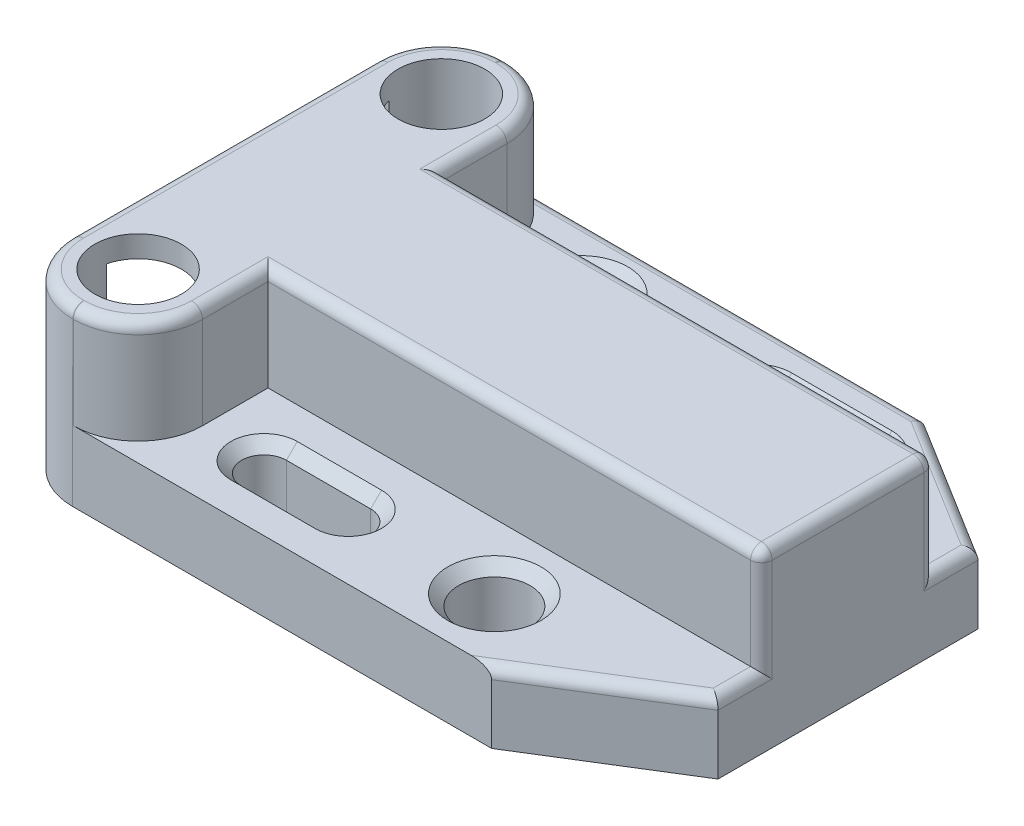
SolidWorks part; units mm, degrees
ref_plane "Front Plane" through (0, 0, 0) normal (0, 0, 1) x (1, 0, 0)
ref_plane "Top Plane" through (0, 0, 0) normal (0, 1, 0) x (1, 0, 0)
ref_plane "Right Plane" through (0, 0, 0) normal (1, 0, 0) x (0, 0, -1)
sketch "Sketch1" plane through (0, 0, 0) normal (0, 1, 0) x (1, 0, 0)
  line L0 (33.1051, 2.8562) -> (46.002, -5.1438)
  line L1 (-3.6889, 2.8562) -> (33.1051, 2.8562)
  line L2 (-11.5449, -3.9662) -> (-11.5449, -29.6573)
  line L3 (-5.3262, -37.1438) -> (33.1051, -37.1438)
  line L4 (33.1051, 2.8562) -> (33.1051, -37.1438)
  line L5 (46.002, -5.1438) -> (46.002, -29.1438)
  line L6 (46.002, -29.1438) -> (33.1051, -37.1438)
  line L10 (-3.6889, 2.8562) -> (-5.5949, 2.8562)
  line L11 (-11.5449, -3.9662) -> (-11.5449, -3.0938)
  line L13 (-11.5449, -29.6573) -> (-11.5449, -31.1938)
  line L14 (-5.5949, -37.1438) -> (-5.3262, -37.1438)
  arc A0 (-11.5449, -31.1938) -> (-5.5949, -37.1438) centre (-5.5949, -31.1938) ccw
  arc A1 (-5.5949, 2.8562) -> (-11.5449, -3.0938) centre (-5.5949, -3.0938) ccw
  point P14 (46.002, -17.1438)
  dimension "D4" = 5.95
  dimension "D1" = 57.5469
  dimension "D2" = 40
  dimension "D3" = 24
  dimension "D5" = 44.65
extrude "Boss-Extrude1" add sketch "Sketch1" along normal blind 6.5 contours L1 A1 L2 L3 L4 | L6 L5 L0 L4 region at (10.9602, 0, 17.1438) region at (39.0162, 0, 17.1438)
sketch "Sketch2" plane through (0, 6.5, 0) normal (0, 1, 0) x (1, 0, 0)
  line L0 (-5.5949, 2.8562) -> (33.1051, 2.8562) construction
  line L1 (46.002, -9.1438) -> (0.4551, -9.1438)
  line L2 (46.002, -9.1438) -> (46.002, -25.1438)
  line L3 (46.002, -25.1438) -> (0.4551, -25.1438)
  line L4 (0.4551, -9.1438) -> (0.4551, -25.1438)
  line L5 (-5.5949, 2.8562) -> (-5.4949, 2.8562)
  line L6 (-11.5449, -3.0938) -> (-11.5449, -31.1938)
  line L7 (-5.5949, -37.1438) -> (-5.4949, -37.1438)
  line L8 (0.4551, -3.0938) -> (0.4551, -31.1938)
  line L9 (-5.5949, -37.1438) -> (33.1051, -37.1438) construction
  line L10 (46.002, -5.1438) -> (46.002, -29.1438) construction
  line L11 (-11.5449, -3.0938) -> (-11.5449, -31.1938) construction
  circle A0 centre (-5.5449, -3.1438) radius 4
  circle A1 centre (-5.5449, -31.1438) radius 4
  arc A3 (-5.5199, -37.1438) -> (0.4551, -31.1938) centre (-5.4949, -31.1938) ccw
  arc A4 (-11.5449, -31.1938) -> (-5.5699, -37.1438) centre (-5.5949, -31.1938) ccw
  arc A5 (-5.4949, 2.8562) -> (0.4551, -3.0938) centre (-5.4949, -3.0938) cw
  arc A6 (-5.5949, 2.8562) -> (-11.5449, -3.0938) centre (-5.5949, -3.0938) ccw
  arc A7 (-5.5199, -37.1438) -> (-5.5699, -37.1438) centre (-5.5449, -43.0937) ccw
  line M1 (33.1051, 2.8562) -> (-5.5949, 2.8562)
  arc M2 (-5.5949, 2.8562) -> (-11.5449, -3.0938) centre (-5.5949, -3.0938) ccw
  line M3 (-11.5449, -3.0938) -> (-11.5449, -31.1938)
  line M7 (46.002, -29.1438) -> (46.002, -5.1438)
  arc M10 (-11.5449, -31.1938) -> (-5.5949, -37.1438) centre (-5.5949, -31.1938) ccw
  dimension "D1" = 8
  dimension "D2" = 8
  dimension "D3" = 6
  dimension "D4" = 6
  dimension "D9" = 6
  dimension "D10" = 5.95
  dimension "D11" = 5.95
  dimension "D7" = 12
  dimension "D8" = 12
extrude "Cut-Extrude1" cut sketch "Sketch2" against normal blind 5.5 contours A0 | A1 region at (-5.5449, 6.5, 3.1438) region at (-5.5449, 6.5, 31.1438)
extrude "Boss-Extrude2" add sketch "Sketch2<3>" along normal blind 9.5 contours A7 A3 L8 L4 A5 A4 A0 A1 M1 M2 M3 M10 | L1 L4 L3 M7 region at (23.2285, 6.5, 17.1438) region at (-5.5449, 6.5, 17.1438)
sketch "Sketch2<3>" plane through (0, 6.5, 0) normal (0, 1, 0) x (1, 0, 0) same geometry as "Sketch2"
sketch "Sketch3" plane through (0, 6.5, 0) normal (0, 1, 0) x (1, 0, 0)
  line L0 (33.1051, 2.8562) -> (-5.4949, 2.8562) construction
  line L1 (-5.5199, -37.1438) -> (33.1051, -37.1438) construction
  line L2 (6.0844, -31.1438) -> (13.8639, -31.1438) construction
  line L3 (6.0844, -29.0762) -> (13.8639, -29.0762)
  line L4 (6.0844, -33.2114) -> (13.8639, -33.2114)
  line L5 (23.4223, -3.1438) -> (32.6699, -3.1438) construction
  line L6 (23.4223, -0.7715) -> (32.6699, -0.7715)
  line L7 (23.4223, -5.5162) -> (32.6699, -5.5162)
  circle A0 centre (7.3707, -3.1438) radius 3.3
  circle A1 centre (27.3504, -31.1438) radius 3.3
  arc A2 (6.0844, -29.0762) -> (6.0844, -33.2114) centre (6.0844, -31.1438) ccw
  arc A3 (13.8639, -33.2114) -> (13.8639, -29.0762) centre (13.8639, -31.1438) ccw
  arc A4 (23.4223, -0.7715) -> (23.4223, -5.5162) centre (23.4223, -3.1438) ccw
  arc A5 (32.6699, -5.5162) -> (32.6699, -0.7715) centre (32.6699, -3.1438) ccw
  point P10 (9.9742, -31.1438)
  point P17 (28.0461, -3.1438)
  dimension "D1" = 6.6
  dimension "D2" = 6.6
  dimension "D4" = 6
  dimension "D3" = 6
  dimension "D5" = 6
  dimension "D6" = 6
extrude "Cut-Extrude2" cut sketch "Sketch3" against normal blind 9.5
chamfer "Chamfer2" distance 1 angle 45 10 edges at (7.3707, 6.5, 6.4438) (35.0422, 6.5, 3.1438) (28.0461, 6.5, 0.7715) (21.0499, 6.5, 3.1438) (28.0461, 6.5, 5.5162) (27.3504, 6.5, 34.4438) (9.9742, 6.5, 33.2114) (15.9315, 6.5, 31.1438) (4.0168, 6.5, 31.1438) (9.9742, 6.5, 29.0762)
fillet "Fillet4" radius 1 17 edges at (0.4551, 16, 28.1688) (-5.5449, 16, -2.8562) (-5.5449, 16, 37.1437) (-1.2876, 16, -1.1135) (0.4551, 16, 6.1188) (23.2285, 16, 25.1438) (46.002, 16, 17.1438) (-11.5449, 16, 17.1438) (-9.8022, 16, -1.1135) (23.2285, 16, 9.1438) (-1.2965, 16, 35.4099) (-9.7933, 16, 35.4099) (39.5535, 6.5, 1.1438)
fillet "Fillet11" radius 1 2 edges
sketch "Sketch4" plane through (-11.5449, 0, 0) normal (-1, 0, 0) x (0, 0, 1)
  line L0 (31.1938, 15) -> (3.0938, 15) construction
  line L1 (4.0938, 14) -> (30.1938, 14)
  line L2 (4.0938, 14) -> (4.0938, 2)
  line L3 (4.0938, 2) -> (30.1938, 2)
  line L4 (30.1938, 14) -> (30.1938, 2)
  line L5 (3.0938, 15) -> (3.0938, 0) construction
  line L6 (31.1938, 15) -> (31.1938, 0) construction
  line L7 (31.1938, 0) -> (3.0938, 0) construction
  dimension "D1" = 1
  dimension "D2" = 1
  dimension "D3" = 1
  dimension "D4" = 2
extrude "Cut-Extrude3" cut sketch "Sketch4" against normal blind 9.5
ref_plane "Plane1" through (46.002, 15, 10.1438) normal (0, 1, 0) x (1, 0, 0)
sketch "Sketch6" plane through (-2.0449, 0, 0) normal (-1, 0, 0) x (0, 0, 1)
  line L0 (3.0938, 16) -> (31.1938, 16) construction
  line L1 (9.758, 13) -> (23.758, 13)
  line L2 (9.758, 13) -> (9.758, 3)
  line L3 (9.758, 3) -> (23.758, 3)
  line L4 (23.758, 13) -> (23.758, 3)
  line L5 (5.0803, 2) -> (29.2073, 2) construction
  dimension "D1" = 14
  dimension "D2" = 1
  dimension "D3" = 3
extrude "Cut-Extrude4" cut sketch "Sketch6" against normal blind 20
sketch "Sketch7" plane through (-2.0449, 0, 0) normal (-1, 0, 0) x (0, 0, 1)
  line L1 (15.258, 13) -> (18.258, 13)
  line L2 (15.258, 13) -> (15.258, 14)
  line L3 (15.258, 14) -> (18.258, 14)
  line L4 (18.258, 13) -> (18.258, 14)
  line L5 (15.258, 3) -> (18.258, 3)
  line L6 (15.258, 3) -> (15.258, 2)
  line L7 (15.258, 2) -> (18.258, 2)
  line L8 (18.258, 3) -> (18.258, 2)
  line L9 (23.758, 13) -> (9.758, 13) construction
  line L10 (9.758, 3) -> (23.758, 3) construction
  line L11 (9.758, 13) -> (9.758, 3) construction
  line L12 (9.758, 13) -> (9.758, 3) construction
  dimension "D1" = 1
  dimension "D2" = 1
  dimension "D3" = 3
  dimension "D4" = 3
  dimension "D5" = 5.5
  dimension "D6" = 5.5
extrude "Cut-Extrude5" cut sketch "Sketch7" against normal blind 20
